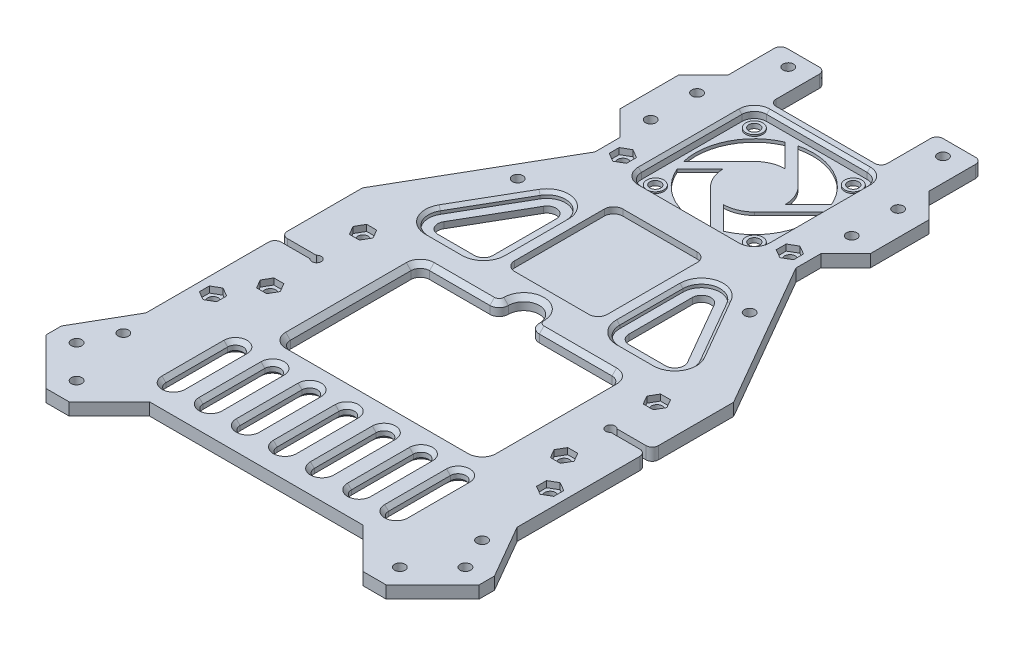
SolidWorks part; units mm, degrees
material "ABS PC"
ref_plane "Front Plane" through (0, 0, 0) normal (0, 0, 1) x (1, 0, 0)
ref_plane "Top Plane" through (0, 0, 0) normal (0, 1, 0) x (1, 0, 0)
ref_plane "Right Plane" through (0, 0, 0) normal (1, 0, 0) x (0, 0, -1)
sketch "Sketch1" plane through (0, 0, 0) normal (0, 1, 0) x (1, 0, 0)
  line L1 (70, -110) -> (-70, -110)
  line L2 (70, -110) -> (70, 110)
  line L3 (70, 110) -> (-70, 110)
  line L4 (-70, -110) -> (-70, 110)
  line L5 (70, -110) -> (-70, 110) construction
  line L6 (70, 110) -> (-70, -110) construction
  point P0 (0, 0)
  dimension "D1" = 220
  dimension "D2" = 140
extrude "Boss-Extrude1" add sketch "Sketch1" along normal blind 4
sketch "Sketch8" plane through (0, 4, 0) normal (0, 1, 0) x (1, 0, 0)
  line L0 (-70, 110) -> (-32.5, 110)
  line L1 (70, 110) -> (-70, 110) construction
  line L2 (-32.5, 110) -> (-32.5, 44.9519)
  line L3 (-32.5, 44.9519) -> (-70, -20)
  line L4 (-70, 110) -> (-70, -110) construction
  line L5 (-70, 110) -> (-70, -20)
  line L6 (0, 110) -> (0, -110) construction
  line L7 (-70, -110) -> (70, -110) construction
  line L8 (70, 110) -> (70, -20)
  line L9 (32.5, 44.9519) -> (70, -20)
  line L10 (32.5, 110) -> (32.5, 44.9519)
  line L11 (70, 110) -> (32.5, 110)
  dimension "D1" = 130
  dimension "D2" = 30
  dimension "D3" = 65
extrude "Cut-Extrude1" cut sketch "Sketch8" against normal blind 5
chamfer "Chamfer3" distance 15 angle 45 2 edges at (70, 2, 110) (-70, 2, 110)
sketch "Sketch48" plane through (0, 4, 0) normal (0, 1, 0) x (1, 0, 0)
  line L0 (32.5, 110) -> (-32.5, 110) construction
  line L1 (34.2449, 70.5) -> (40.5, 70.5) construction
  line L2 (32.5, 53) -> (32.5, 88)
  line L4 (32.5, 88) -> (40.5, 80)
  line L5 (40.5, 80) -> (40.5, 61)
  line L6 (32.5, 53) -> (40.5, 61)
  line L7 (0, 71.0199) -> (0, 60.9015) construction
  line L8 (-32.5, 53) -> (-40.5, 61)
  line L9 (-40.5, 80) -> (-40.5, 61)
  line L10 (-32.5, 88) -> (-40.5, 80)
  line L11 (-32.5, 53) -> (-32.5, 88)
  line L13 (32.5, 110) -> (32.5, 44.9519) construction
  point P16 (-32.5, 70.5)
  dimension "D1" = 45
  dimension "D2" = 8
  dimension "D3" = 35
  dimension "D4" = 39.5
extrude "Boss-Extrude4" add sketch "Sketch48" against normal up to surface (4 mm away) up to face at (0, 0, 14.0096)
sketch "Sketch10" plane through (0, 0, 0) normal (0, 1, 0) x (1, 0, 0)
  line L0 (0, 110) -> (0, -110) construction
  line L1 (32.5, 110) -> (-32.5, 110) construction
  line L2 (-55, -110) -> (55, -110) construction
  line L3 (-32.5, 78) -> (-32.5, 63) construction
  line L4 (-62.5, -102.5) -> (-57.5503, -97.5503) construction
  line L5 (-62.8536, -92.247) -> (-52.247, -102.8536) construction
  line L6 (-70, -95) -> (-55, -110) construction
  point P9 (32.5, 63)
  point P10 (32.5, 78)
  point P17 (52.247, -102.8536)
  point P18 (62.8536, -92.247)
  dimension "D1" = 15
  dimension "D2" = 65
  dimension "D3" = 32
  dimension "D4" = 15
  dimension "D5" = 7
sketch "Sketch15" plane through (0, 4, 0) normal (0, 1, 0) x (1, 0, 0)
  line L0 (0, 110) -> (0, -110) construction
  line L1 (32.5, 110) -> (-32.5, 110) construction
  line L2 (-55, -110) -> (55, -110) construction
  line L3 (25, 100) -> (-25, 100) construction
  line L4 (37.5, 25) -> (-37.5, 25) construction
  line L5 (58, -57) -> (-58, -57) construction
  point P9 (0, 100)
  point P13 (0, 25)
  point P15 (0, -57)
  dimension "D1" = 50
  dimension "D2" = 10
  dimension "D3" = 75
  dimension "D4" = 85
  dimension "D5" = 116
  dimension "D6" = 167
hole_wizard "CSK for M3 Flat Head Machine Screw3" positions "Sketch16" profile "Sketch17" countersink size "M3" standard "ANSI Metric"
sketch "Sketch16" plane through (0, 0, 0) normal (0, 1, 0) x (1, 0, 0)
  point P6 (37.5, 25)
  point P9 (-37.5, 25)
  point P12 (-25, 100)
  point P15 (25, 100)
sketch "Sketch17" plane through (37.5, 0, -25) normal (1, 0, 0) x (0, 0, -1)
  line L0 (0, 0) -> (0, 6.0215)
  line L1 (0, 6.0215) -> (1.7, 5)
  line L2 (1.7, 5) -> (1.7, 1.45)
  line L3 (1.7, 1.45) -> (3.15, 0)
  line L5 (3.15, 0) -> (0, 0)
  line L6 (-1.7, 1.45) -> (-3.15, 0) construction
  line L10 (0, 6.0215) -> (-1.7, 5) construction
  line L11 (0, -6.35) -> (0, 107.95) construction
  dimension "Hole Dia." = 3.4
  dimension "Hole Depth" = 5
  dimension "Near C'Sink Dia." = 6.3
  dimension "Near C'Sink Angle" = 90
  dimension "Drill Angle" = 118
sketch "Sketch18" plane through (0, 4, 0) normal (0, 1, 0) x (1, 0, 0)
  line L0 (32.5, 110) -> (-32.5, 110) construction
  line L1 (-46.4338, 114.6286) -> (34.8035, 114.6286)
  line L2 (-46.4338, 114.6286) -> (-46.4338, 105)
  line L3 (-46.4338, 105) -> (34.8035, 105)
  line L4 (34.8035, 114.6286) -> (34.8035, 105)
  dimension "D1" = 5
extrude "Cut-Extrude2" cut sketch "Sketch18" against normal blind 5
sketch "Sketch34" plane through (0, 4, 0) normal (0, 1, 0) x (1, 0, 0)
  line L0 (-70, -20) -> (-60, -2.6795)
  line L1 (-70, -20) -> (-32.5, 44.9519) construction
  line L2 (-60, -2.6795) -> (-60, -72.6795)
  line L3 (-60, -72.6795) -> (-70, -90)
  line L4 (-70, -20) -> (-70, -95) construction
  line L5 (-70, -90) -> (-70, -20)
  line L6 (0, -90.4055) -> (0, -61.6307) construction
  line L7 (70, -90) -> (70, -20)
  line L8 (60, -72.6795) -> (70, -90)
  line L9 (60, -2.6795) -> (60, -72.6795)
  line L10 (70, -20) -> (60, -2.6795)
  line L11 (-55, -110) -> (55, -110) construction
  dimension "D1" = 120
  dimension "D2" = 20
extrude "Cut-Extrude8" cut sketch "Sketch34" against normal blind 10
chamfer "Chamfer4" [suppressed] distance 20 angle 30
sketch "Sketch35" plane through (0, 4, 0) normal (0, 1, 0) x (1, 0, 0)
  line L1 (-30.5, -58.5) -> (34.5, -58.5)
  line L2 (-30.5, -58.5) -> (-30.5, -13.5)
  line L3 (-30.5, -13.5) -> (34.5, -13.5)
  line L4 (34.5, -58.5) -> (34.5, -13.5)
  line L5 (-30.5, -58.5) -> (34.5, -13.5) construction
  line L6 (-30.5, -13.5) -> (34.5, -58.5) construction
  point P0 (2, -36)
  dimension "D1" = 2
  dimension "D2" = 65
  dimension "D3" = 45
  dimension "D4" = 36
extrude "Cut-Extrude9" cut sketch "Sketch35" against normal through all
fillet "Fillet1" radius 3 4 edges at (-30.5, 2, 58.5) (-30.5, 2, 13.5) (34.5, 2, 13.5) (34.5, 2, 58.5)
sketch "Sketch36" plane through (0, 4, 0) normal (0, 1, 0) x (1, 0, 0)
  line L0 (0, -110) -> (0, -97) construction
  line L1 (-55, -110) -> (55, -110) construction
  line L2 (-47.5, -110) -> (-34.5, -97)
  line L3 (-34.5, -97) -> (34.5, -97)
  line L4 (-47.5, -110) -> (47.5, -110)
  line L6 (-70, -95) -> (-55, -110) construction
  line L7 (47.5, -110) -> (34.5, -97)
  dimension "D1" = 13
  dimension "D2" = 95
extrude "Cut-Extrude10" cut sketch "Sketch36" against normal through all
sketch "Sketch38" plane through (0, 0, 0) normal (0, -1, 0) x (1, 0, 0)
  line L0 (0, -105) -> (0, -90) construction
  line L1 (-32.5, -105) -> (32.5, -105) construction
  line L2 (18, -87) -> (-18, -87)
  line L3 (-18, -87) -> (-18, -105)
  line L4 (-18, -105) -> (18, -105)
  line L5 (18, -87) -> (18, -105)
  dimension "D1" = 90
  dimension "D2" = 18
  dimension "D3" = 36
extrude "Cut-Extrude14" cut sketch "Sketch38" against normal through all
sketch "Sketch39" plane through (0, 0, 0) normal (0, -1, 0) x (1, 0, 0)
  line L0 (0, 37.973) -> (0, 15.9654) construction
  circle A0 centre (-47.5, 30) radius 1.5
  circle A1 centre (47.5, 30) radius 1.5
  dimension "D1" = 95
  dimension "D2" = 3
  dimension "D3" = 30
extrude "Cut-Extrude15" cut sketch "Sketch39" against normal through all
hole_wizard "CSK for M3 Flat Head Machine Screw2" positions "Sketch40" profile "Sketch41" countersink size "M3" standard "ANSI Metric"
sketch "Sketch40" plane through (0, 0, 0) normal (0, -1, 0) x (-1, 0, 0)
  point P0 (-58, -82)
  point P3 (58, -82)
sketch "Sketch41" plane through (58, 0, 82) normal (1, 0, 0) x (0, 0, -1)
  line L0 (0, 0) -> (0, 11.0215)
  line L1 (0, 11.0215) -> (1.7, 10)
  line L2 (1.7, 10) -> (1.7, 1.45)
  line L3 (1.7, 1.45) -> (3.15, 0)
  line L5 (3.15, 0) -> (0, 0)
  line L6 (-1.7, 1.45) -> (-3.15, 0) construction
  line L10 (0, 11.0215) -> (-1.7, 10) construction
  line L11 (0, -6.35) -> (0, 107.95) construction
  dimension "Hole Dia." = 3.4
  dimension "Hole Depth" = 10
  dimension "Near C'Sink Dia." = 6.3
  dimension "Near C'Sink Angle" = 90
  dimension "Drill Angle" = 118
hole_wizard "Ø3.5 (3.5) Diameter Hole1" positions "Sketch45" profile "Sketch46" hole size "Ø3.5" standard "ANSI Metric"
sketch "Sketch45" plane through (0, 4, 0) normal (0, 1, 0) x (1, 0, 0)
  line L0 (-32.5, 44.9519) -> (-32.5, 53) construction
  line L1 (-60, -72.6795) -> (-60, -2.6795) construction
  line L2 (-32.5, 105) -> (-18, 105) construction
  point P0 (-54.5, -56.5)
  point P2 (-27, 48.5)
  dimension "D1" = 5.5
  dimension "D2" = 5.5
  dimension "D3" = 56.5
  dimension "D4" = 105
sketch "Sketch46" plane through (-54.5, 4, 56.5) normal (1, 0, 0) x (0, 0, 1)
  line L0 (0, 0) -> (0, 6.0515)
  line L1 (0, 6.0515) -> (1.75, 5)
  line L2 (1.75, 5) -> (1.75, 0)
  line L5 (1.75, 0) -> (0, 0)
  line L10 (0, 6.0515) -> (-1.75, 5) construction
  line L11 (0, -6.35) -> (0, 107.95) construction
  dimension "Hole Dia." = 3.5
  dimension "Hole Depth" = 5
  dimension "Drill Angle" = 118
mirror "Mirror1" about plane through (0, 0, 0) normal (1, 0, 0) of "Ø3.5 (3.5) Diameter Hole1"
sketch "Sketch47" plane through (0, 4, 0) normal (0, 1, 0) x (1, 0, 0)
  line L0 (0, 13.2168) -> (0, -3.9151) construction
  line L1 (29.8, 46.8834) -> (29.8, 50.1166)
  line L2 (29.8, 50.1166) -> (27, 51.7332)
  line L3 (27, 51.7332) -> (24.2, 50.1166)
  line L4 (24.2, 50.1166) -> (24.2, 46.8834)
  line L5 (24.2, 46.8834) -> (27, 45.2668)
  line L6 (27, 45.2668) -> (29.8, 46.8834)
  line L7 (57.3, -58.1166) -> (57.3, -54.8834)
  line L8 (57.3, -54.8834) -> (54.5, -53.2668)
  line L9 (54.5, -53.2668) -> (51.7, -54.8834)
  line L10 (51.7, -54.8834) -> (51.7, -58.1166)
  line L11 (51.7, -58.1166) -> (54.5, -59.7332)
  line L12 (54.5, -59.7332) -> (57.3, -58.1166)
  line L13 (-54.5, -59.7332) -> (-57.3, -58.1166)
  line L14 (-51.7, -58.1166) -> (-54.5, -59.7332)
  line L15 (-51.7, -54.8834) -> (-51.7, -58.1166)
  line L16 (-54.5, -53.2668) -> (-51.7, -54.8834)
  line L17 (-57.3, -54.8834) -> (-54.5, -53.2668)
  line L18 (-57.3, -58.1166) -> (-57.3, -54.8834)
  line L19 (-27, 45.2668) -> (-29.8, 46.8834)
  line L20 (-24.2, 46.8834) -> (-27, 45.2668)
  line L21 (-24.2, 50.1166) -> (-24.2, 46.8834)
  line L22 (-27, 51.7332) -> (-24.2, 50.1166)
  line L23 (-29.8, 50.1166) -> (-27, 51.7332)
  line L24 (-29.8, 46.8834) -> (-29.8, 50.1166)
  circle A0 centre (27, 48.5) radius 2.8 construction
  circle A1 centre (54.5, -56.5) radius 2.8 construction
  circle A2 centre (-54.5, -56.5) radius 2.8 construction
  circle A3 centre (-27, 48.5) radius 2.8 construction
  dimension "D1" = 5.6
extrude "Cut-Extrude16" cut sketch "Sketch47" against normal blind 2
hole_wizard "CSK for M3 Flat Head Machine Screw1" positions "Sketch52" profile "Sketch53" countersink size "M3" standard "ANSI Metric"
sketch "Sketch52" plane through (0, 0, 0) normal (0, -1, 0) x (-1, 0, 0)
  point P0 (32.5, 63)
  point P3 (32.5, 78)
  point P6 (-32.5, 78)
  point P9 (-32.5, 63)
  point P12 (62.8536, -92.247)
  point P15 (52.247, -102.8536)
  point P18 (-52.247, -102.8536)
  point P21 (-62.8536, -92.247)
sketch "Sketch53" plane through (-32.5, 0, -63) normal (1, 0, 0) x (0, 0, -1)
  line L0 (0, 0) -> (0, 6.0215)
  line L1 (0, 6.0215) -> (1.7, 5)
  line L2 (1.7, 5) -> (1.7, 1.45)
  line L3 (1.7, 1.45) -> (3.15, 0)
  line L5 (3.15, 0) -> (0, 0)
  line L6 (-1.7, 1.45) -> (-3.15, 0) construction
  line L10 (0, 6.0215) -> (-1.7, 5) construction
  line L11 (0, -6.35) -> (0, 107.95) construction
  dimension "Hole Dia." = 3.4
  dimension "Hole Depth" = 5
  dimension "Near C'Sink Dia." = 6.3
  dimension "Near C'Sink Angle" = 90
  dimension "Drill Angle" = 118
sketch "Sketch54" plane through (0, 4, 0) normal (0, 1, 0) x (1, 0, 0)
  line L0 (0, -24.4413) -> (0, -37.1235) construction
  circle A0 centre (-47.5, -30) radius 7.5
  circle A1 centre (-47.5, -30) radius 1.5
  circle A2 centre (-47.5, -30) radius 1.5 construction
  circle A3 centre (47.5, -30) radius 1.5
  circle A4 centre (47.5, -30) radius 7.5
  dimension "D1" = 15
extrude "Cut-Extrude17" [suppressed] cut sketch "Sketch54" against normal blind 2
hole_wizard "Ø3.5 (3.5) Diameter Hole2" positions "Sketch55" profile "Sketch56" hole size "Ø3.5" standard "ANSI Metric" end condition through all
sketch "Sketch55" plane through (0, 4, 0) normal (0, 1, 0) x (1, 0, 0)
  line L1 (16, 80) -> (-16, 80) construction
  line L2 (16, 80) -> (16, 48) construction
  line L3 (16, 48) -> (-16, 48) construction
  line L4 (-16, 80) -> (-16, 48) construction
  line L5 (0, 48) -> (0, 0) construction
  point P1 (16, 80)
  point P2 (-16, 48)
  point P5 (16, 48)
  point P6 (-16, 80)
  dimension "D1" = 32
  dimension "D2" = 48
sketch "Sketch56" plane through (16, 4, -80) normal (1, 0, 0) x (0, 0, 1)
  line L0 (0, 0) -> (0, 4)
  line L1 (0, 4) -> (1.75, 4)
  line L2 (1.75, 4) -> (1.75, 0)
  line L5 (1.75, 0) -> (0, 0)
  line L11 (0, -6.35) -> (0, 107.95) construction
  dimension "Thru Hole Dia." = 3.5
  dimension "Thru Hole Depth" = 4
sketch "Sketch57" plane through (0, 4, 0) normal (0, 1, 0) x (1, 0, 0)
  line L0 (-16, 80) -> (16, 48) construction
  line L1 (9.9995, 64.1) -> (17.4397, 71.5402)
  line L2 (7.0711, 56.9289) -> (18.4947, 68.3526)
  line L3 (0.1, 54.0005) -> (7.5402, 46.5603)
  line L4 (-7.0711, 56.9289) -> (4.3526, 45.5053)
  line L5 (-9.9995, 63.9) -> (-17.4397, 56.4598)
  line L6 (-7.0711, 71.0711) -> (-18.4947, 59.6474)
  line L7 (-0.1, 73.9995) -> (-7.5402, 81.4397)
  line L8 (7.0711, 71.0711) -> (-4.3526, 82.4947)
  line L9 (0, 58.5149) -> (0, 69.4851) construction
  circle A0 centre (0, 64) radius 19
  circle A1 centre (0, 64) radius 10
  point P31 (0, 64)
  dimension "D1" = 38
  dimension "D2" = 20
  dimension "D3" = 3
  dimension "D5" = 135
  dimension "D4" = 4
extrude "Cut-Extrude18" cut sketch "Sketch57" against normal blind 10 contours A1 L7 A0 L6 | A1 L1 A0 L8 | A1 L3 A0 L2 | A1 L5 A0 L4 region at (7.9912, 4, -75.4298) region at (11.4298, 4, -56.0088) region at (-11.4298, 4, -71.9912) region at (-7.9912, 4, -52.5702)
sketch "Sketch58" plane through (0, 4, 0) normal (0, 1, 0) x (1, 0, 0)
  line L1 (-16.25, 43.75) -> (16.25, 43.75)
  line L2 (-20.25, 47.75) -> (-20.25, 80.25)
  line L3 (-16.25, 84.25) -> (16.25, 84.25)
  line L4 (20.25, 47.75) -> (20.25, 80.25)
  line L5 (-20.25, 43.75) -> (20.25, 84.25) construction
  line L6 (-20.25, 84.25) -> (20.25, 43.75) construction
  arc A0 (-20.25, 47.75) -> (-16.25, 43.75) centre (-16.25, 47.75) ccw
  arc A1 (16.25, 43.75) -> (20.25, 47.75) centre (16.25, 47.75) ccw
  arc A2 (20.25, 80.25) -> (16.25, 84.25) centre (16.25, 80.25) ccw
  arc A3 (-16.25, 84.25) -> (-20.25, 80.25) centre (-16.25, 80.25) ccw
  point P0 (0, 64)
  dimension "D2" = 4
  dimension "D1" = 40.5
extrude "Cut-Extrude20" cut sketch "Sketch58" against normal offset from surface (3 mm away) 1 up to face at (8.2079, 0, -73.363)
sketch "Sketch59" plane through (0, 0, 0) normal (0, -1, 0) x (1, 0, 0)
  line L0 (31.5, 13.5) -> (-27.5, 13.5) construction
  line L1 (5, 10.5) -> (-5, 10.5)
  line L2 (5, 10.5) -> (5, 13.5)
  line L3 (5, 13.5) -> (-5, 13.5)
  line L4 (-5, 10.5) -> (-5, 13.5)
  line L5 (5, 10.5) -> (-5, 13.5) construction
  line L6 (5, 13.5) -> (-5, 10.5) construction
  line L7 (0, 0) -> (0, 12) construction
  arc A0 (-5, 10.5) -> (5, 10.5) centre (0, 10.5) ccw
  point P0 (0, 12)
  dimension "D1" = 3
  dimension "D2" = 10
extrude "Cut-Extrude21" cut sketch "Sketch59" against normal blind 10 contours L4 L1 L2 L3 | L1 A0 region at (0, 0, 8.3779) region at (0, 0, 12)
fillet "Fillet5" radius 3 2 edges at (5, 2, 13.5) (-5, 2, 13.5)
sketch "Sketch60" plane through (0, 0, 0) normal (0, -1, 0) x (1, 0, 0)
  line L0 (-42, 1.5) -> (-22, 1.5)
  line L1 (-22, 1.5) -> (-22, -33.141)
  line L2 (-22, -33.141) -> (-42, 1.5)
  line L3 (0, 28.7462) -> (0, 44.2491) construction
  line L4 (22, -33.141) -> (42, 1.5)
  line L5 (22, 1.5) -> (22, -33.141)
  line L6 (42, 1.5) -> (22, 1.5)
  line L7 (-8, 13.5) -> (-27.5, 13.5) construction
  line L8 (-60, 2.6795) -> (-32.5, -44.9519) construction
  dimension "D1" = 20
  dimension "D2" = 44
  dimension "D3" = 12
  dimension "D4" = 34.641
extrude "Cut-Extrude22" cut sketch "Sketch60" against normal through all
fillet "Fillet6" radius 3 6 edges at (42, 2, 1.5) (22, 2, -33.141) (22, 2, 1.5) (-22, 2, 1.5) (-22, 2, -33.141) (-42, 2, 1.5)
fillet "Fillet7" radius 2 6 edges at (32.5, 2, -105) (-32.5, 2, -105) (18, 2, -105) (18, 2, -87) (-18, 2, -87) (-18, 2, -105)
sketch "Sketch61" plane through (0, 1, 0) normal (0, 1, 0) x (1, 0, 0)
  circle A1 centre (-16, 80) radius 2.75
  circle A2 centre (-16, 80) radius 1.75 construction
  circle A3 centre (16, 80) radius 2.75
  circle A4 centre (16, 48) radius 2.75
  circle A5 centre (-16, 48) radius 2.75
  circle A9 centre (-16, 80) radius 1.75
  circle A10 centre (-16, 80) radius 1.75
  circle A12 centre (16, 80) radius 1.75
  circle A13 centre (16, 80) radius 1.75
  circle A15 centre (16, 48) radius 1.75
  circle A16 centre (16, 48) radius 1.75
  circle A18 centre (-16, 48) radius 1.75
  circle A19 centre (-16, 48) radius 1.75
  dimension "D1" = 1
  dimension "D2" = 0
  dimension "D3" = 0
  dimension "D4" = 0
  dimension "D5" = 0
extrude "Boss-Extrude5" add sketch "Sketch61" along normal blind 0.5
sketch "Sketch62" plane through (0, 4, 0) normal (0, 1, 0) x (1, 0, 0)
  line L44 (0, 12.7981) -> (0, -1.7616) construction
  line L45 (36.8038, -4.5) -> (25, -4.5)
  line L46 (30.1962, 24.9449) -> (42, 4.5)
  line L47 (-19, 1.5) -> (-19, 21.9449)
  line L48 (-30.1962, 24.9449) -> (-42, 4.5)
  line L49 (-36.8038, -4.5) -> (-25, -4.5)
  line L50 (-19, 1.5) -> (-19, 21.9449)
  line L51 (-30.1962, 24.9449) -> (-42, 4.5)
  line L52 (-36.8038, -4.5) -> (-25, -4.5)
  line L53 (19, 1.5) -> (19, 21.9449)
  arc A13 (19, 21.9449) -> (30.1962, 24.9449) centre (25, 21.9449) cw
  arc A14 (42, 4.5) -> (36.8038, -4.5) centre (36.8038, 1.5) cw
  arc A15 (25, -4.5) -> (19, 1.5) centre (25, 1.5) cw
  arc A16 (-25, -4.5) -> (-19, 1.5) centre (-25, 1.5) ccw
  arc A17 (-42, 4.5) -> (-36.8038, -4.5) centre (-36.8038, 1.5) ccw
  arc A18 (-19, 21.9449) -> (-30.1962, 24.9449) centre (-25, 21.9449) ccw
  arc A19 (-25, -4.5) -> (-19, 1.5) centre (-25, 1.5) ccw
  arc A20 (-42, 4.5) -> (-36.8038, -4.5) centre (-36.8038, 1.5) ccw
  arc A21 (-19, 21.9449) -> (-30.1962, 24.9449) centre (-25, 21.9449) ccw
  dimension "D1" = 3
extrude "Cut-Extrude23" cut sketch "Sketch62" against normal offset from surface (2 mm away) 2 up to face at (-28.8177, 0, -7.9444)
hole_wizard "Ø3.5 (3.5) Diameter Hole3" positions "Sketch64" profile "Sketch65" hole size "Ø3.5" standard "ANSI Metric" end condition through all
sketch "Sketch64" plane through (0, 0, 0) normal (0, -1, 0) x (-1, 0, 0)
  line L0 (47.5, -30) -> (47.5, -45) construction
  line L1 (47.5, -30) -> (46, -30) construction
  line L3 (0, -31.9374) -> (0, -51.0019) construction
  circle A0 centre (47.5, -30) radius 1.5 construction
  point P2 (47.5, -45)
  point P22 (47.5, -15)
  point P28 (-47.5, -15)
  point P29 (-47.5, -45)
  dimension "D1" = 30
sketch "Sketch65" plane through (47.5, 0, 45) normal (1, 0, 0) x (0, 0, -1)
  line L0 (0, 0) -> (0, 4)
  line L1 (0, 4) -> (1.75, 4)
  line L2 (1.75, 4) -> (1.75, 0)
  line L5 (1.75, 0) -> (0, 0)
  line L11 (0, -6.35) -> (0, 107.95) construction
  dimension "Thru Hole Dia." = 3.5
  dimension "Thru Hole Depth" = 4
sketch "Sketch66" plane through (0, 4, 0) normal (0, 1, 0) x (1, 0, 0)
  line L0 (-47.5, -30) -> (-38.51, -30) construction
  line L1 (-44.2668, -15) -> (-45.8834, -12.2)
  line L2 (-45.8834, -12.2) -> (-49.1166, -12.2)
  line L3 (-49.1166, -12.2) -> (-50.7332, -15)
  line L4 (-50.7332, -15) -> (-49.1166, -17.8)
  line L5 (-49.1166, -17.8) -> (-45.8834, -17.8)
  line L6 (-45.8834, -17.8) -> (-44.2668, -15)
  line L7 (-45.8834, -42.2) -> (-44.2668, -45)
  line L8 (-49.1166, -42.2) -> (-45.8834, -42.2)
  line L9 (-50.7332, -45) -> (-49.1166, -42.2)
  line L10 (-49.1166, -47.8) -> (-50.7332, -45)
  line L11 (-45.8834, -47.8) -> (-49.1166, -47.8)
  line L12 (-44.2668, -45) -> (-45.8834, -47.8)
  line L13 (0, -21.6578) -> (0, -42.5) construction
  line L14 (44.2668, -45) -> (45.8834, -47.8)
  line L15 (45.8834, -47.8) -> (49.1166, -47.8)
  line L16 (49.1166, -47.8) -> (50.7332, -45)
  line L17 (50.7332, -45) -> (49.1166, -42.2)
  line L18 (49.1166, -42.2) -> (45.8834, -42.2)
  line L19 (45.8834, -42.2) -> (44.2668, -45)
  line L20 (45.8834, -17.8) -> (44.2668, -15)
  line L21 (49.1166, -17.8) -> (45.8834, -17.8)
  line L22 (50.7332, -15) -> (49.1166, -17.8)
  line L23 (49.1166, -12.2) -> (50.7332, -15)
  line L24 (45.8834, -12.2) -> (49.1166, -12.2)
  line L25 (44.2668, -15) -> (45.8834, -12.2)
  circle A0 centre (-47.5, -15) radius 2.8 construction
  dimension "D1" = 5.6
extrude "Cut-Extrude24" cut sketch "Sketch66" against normal blind 2
sketch "Sketch67" plane through (0, 0, 0) normal (0, -1, 0) x (1, 0, 0)
  line L0 (-47.5, 30) -> (-60, 30) construction
  line L1 (-60, 72.6795) -> (-60, 2.6795) construction
  line L2 (-60, 31) -> (-48.618, 31)
  line L3 (-60, 31) -> (-60, 29)
  line L4 (-60, 29) -> (-48.618, 29)
  circle A0 centre (-47.5, 30) radius 1.5 construction
  circle A3 centre (-47.5, 30) radius 1.5
  circle A4 centre (-47.5, 30) radius 1.5
  dimension "D1" = 2
  dimension "D2" = 0
extrude "Cut-Extrude25" cut sketch "Sketch67" against normal through all contours A4 L0 L3 L4 | L0 A4 L2 L3 region at (-54.4394, 0, 29.4972) region at (-54.4394, 0, 30.5028)
mirror "Mirror2" about plane through (0, 0, 0) normal (1, 0, 0) of "Cut-Extrude25"
sketch "Sketch68" plane through (0, 0, 0) normal (0, -1, 0) x (1, 0, 0)
  line L0 (0, 97) -> (0, 58.5) construction
  line L1 (-36, 67.75) -> (-36, 87.75) construction
  line L2 (-38.5, 67.75) -> (-38.5, 87.75)
  line L3 (-33.5, 67.75) -> (-33.5, 87.75)
  line L4 (-24, 67.75) -> (-24, 87.75) construction
  line L5 (-26.5, 67.75) -> (-26.5, 87.75)
  line L6 (-21.5, 67.75) -> (-21.5, 87.75)
  line L7 (-12, 67.75) -> (-12, 87.75) construction
  line L8 (-14.5, 67.75) -> (-14.5, 87.75)
  line L9 (-9.5, 67.75) -> (-9.5, 87.75)
  line L10 (0, 67.75) -> (0, 87.75) construction
  line L11 (-2.5, 67.75) -> (-2.5, 87.75)
  line L12 (2.5, 67.75) -> (2.5, 87.75)
  line L13 (12, 67.75) -> (12, 87.75) construction
  line L14 (9.5, 67.75) -> (9.5, 87.75)
  line L15 (14.5, 67.75) -> (14.5, 87.75)
  line L16 (24, 67.75) -> (24, 87.75) construction
  line L17 (21.5, 67.75) -> (21.5, 87.75)
  line L18 (26.5, 67.75) -> (26.5, 87.75)
  line L19 (36, 67.75) -> (36, 87.75) construction
  line L20 (33.5, 67.75) -> (33.5, 87.75)
  line L21 (38.5, 67.75) -> (38.5, 87.75)
  line L22 (34.5, 97) -> (-34.5, 97) construction
  line L23 (-27.5, 58.5) -> (31.5, 58.5) construction
  arc A0 (-38.5, 67.75) -> (-33.5, 67.75) centre (-36, 67.75) ccw
  arc A1 (-33.5, 87.75) -> (-38.5, 87.75) centre (-36, 87.75) ccw
  arc A2 (-26.5, 67.75) -> (-21.5, 67.75) centre (-24, 67.75) ccw
  arc A3 (-21.5, 87.75) -> (-26.5, 87.75) centre (-24, 87.75) ccw
  arc A4 (-14.5, 67.75) -> (-9.5, 67.75) centre (-12, 67.75) ccw
  arc A5 (-9.5, 87.75) -> (-14.5, 87.75) centre (-12, 87.75) ccw
  arc A6 (-2.5, 67.75) -> (2.5, 67.75) centre (0, 67.75) ccw
  arc A7 (2.5, 87.75) -> (-2.5, 87.75) centre (0, 87.75) ccw
  arc A8 (9.5, 67.75) -> (14.5, 67.75) centre (12, 67.75) ccw
  arc A9 (14.5, 87.75) -> (9.5, 87.75) centre (12, 87.75) ccw
  arc A10 (21.5, 67.75) -> (26.5, 67.75) centre (24, 67.75) ccw
  arc A11 (26.5, 87.75) -> (21.5, 87.75) centre (24, 87.75) ccw
  arc A12 (33.5, 67.75) -> (38.5, 67.75) centre (36, 67.75) ccw
  arc A13 (38.5, 87.75) -> (33.5, 87.75) centre (36, 87.75) ccw
  point P5 (-36, 77.75)
  point P10 (0, 79.6664)
  point P13 (0, 97)
  point P14 (-24, 77.75)
  point P21 (-12, 77.75)
  point P28 (0, 77.75)
  point P35 (12, 77.75)
  point P42 (24, 77.75)
  point P49 (36, 77.75)
  point P56 (0, 58.5)
  point P59 (-19.6583, 73.8033)
  point P60 (0, 64.2216)
  point P61 (-31.1889, 77.75)
  point P62 (-30.4581, 77.75)
  dimension "D1" = 20
  dimension "D2" = 5
  dimension "D4" = 7
  dimension "D3" = 7
extrude "Cut-Extrude26" cut sketch "Sketch68" against normal through all
chamfer "Chamfer5" distance 1.5 angle 45 12 edges at (-30.5, 4, 36) (-29.6213, 4, 57.6213) (-29.6213, 4, 14.3787) (2, 4, 58.5) (-17.75, 4, 13.5) (33.6213, 4, 57.6213) (-5.8787, 4, 12.6213) (34.5, 4, 36) (0, 4, 5.5) (33.6213, 4, 14.3787) (5.8787, 4, 12.6213) (19.75, 4, 13.5)
chamfer "Chamfer6" distance 1.25 angle 45 56 edges at (-33.5, 4, 77.75) (-36, 4, 90.25) (-36, 4, 65.25) (-38.5, 4, 77.75) (-33.5, 0, 77.75) (-36, 0, 90.25) (-36, 0, 65.25) (-38.5, 0, 77.75) (-21.5, 4, 77.75) (-24, 4, 90.25) (-24, 4, 65.25) (-26.5, 4, 77.75) (-21.5, 0, 77.75) (-24, 0, 90.25) (-24, 0, 65.25) (-26.5, 0, 77.75) (-9.5, 4, 77.75) (-12, 4, 90.25) (-12, 4, 65.25) (-14.5, 4, 77.75) (-9.5, 0, 77.75) (-12, 0, 90.25) (-12, 0, 65.25) (-14.5, 0, 77.75) (2.5, 4, 77.75) (0, 4, 90.25) (0, 4, 65.25) (-2.5, 4, 77.75) (2.5, 0, 77.75) (0, 0, 90.25) (0, 0, 65.25) (-2.5, 0, 77.75) (14.5, 4, 77.75) (12, 4, 90.25) (12, 4, 65.25) (9.5, 4, 77.75) (14.5, 0, 77.75) (12, 0, 90.25) (12, 0, 65.25) (9.5, 0, 77.75) (26.5, 4, 77.75) (24, 4, 90.25) (24, 4, 65.25) (21.5, 4, 77.75) (26.5, 0, 77.75) (24, 0, 90.25) (24, 0, 65.25) (21.5, 0, 77.75) (38.5, 4, 77.75) (36, 4, 90.25) (36, 4, 65.25) (33.5, 4, 77.75) (38.5, 0, 77.75) (36, 0, 90.25) (36, 0, 65.25) (33.5, 0, 77.75)
sketch "Sketch69" plane through (0, 4, 0) normal (0, 1, 0) x (1, 0, 0)
  line L0 (-25, -1.5) -> (-36.8038, -1.5) construction
  line L1 (15, 33.5) -> (-15, 33.5)
  line L2 (15, 33.5) -> (15, -1.5)
  line L3 (15, -1.5) -> (-15, -1.5)
  line L4 (-15, 33.5) -> (-15, -1.5)
  line L5 (15, 33.5) -> (-15, -1.5) construction
  line L6 (15, -1.5) -> (-15, 33.5) construction
  line L7 (0, 16) -> (0, 0) construction
  point P0 (0, 16)
  dimension "D1" = 30
  dimension "D2" = 35
extrude "Cut-Extrude27" cut sketch "Sketch69" against normal offset from surface (2 mm away) 2 up to face at (-36, 0, 77.75)
fillet "Fillet8" radius 3 4 edges at (-15, 3, 1.5) (15, 3, 1.5) (15, 3, -33.5) (-15, 3, -33.5)
chamfer "Chamfer7" distance 1 angle 45 8 edges at (0, 4, -43.75) (19.0784, 4, -44.9216) (-19.0784, 4, -44.9216) (20.25, 4, -64) (-20.25, 4, -64) (19.0784, 4, -83.0784) (-19.0784, 4, -83.0784) (0, 4, -84.25)
chamfer "Chamfer8" distance 1 angle 45 12 edges at (42, 4, 1.5) (36.0981, 4, -14.7224) (30.9019, 4, 4.5) (23.4471, 4, -27.7404) (20.7574, 4, 2.7426) (19, 4, -11.7224) (-20.7574, 4, 2.7426) (-19, 4, -11.7224) (-30.9019, 4, 4.5) (-23.4471, 4, -27.7404) (-42, 4, 1.5) (-36.0981, 4, -14.7224)
fillet "Fillet9" radius 2 4 edges at (60, 2, 31) (60, 2, 29) (-60, 2, 31) (-60, 2, 29)
